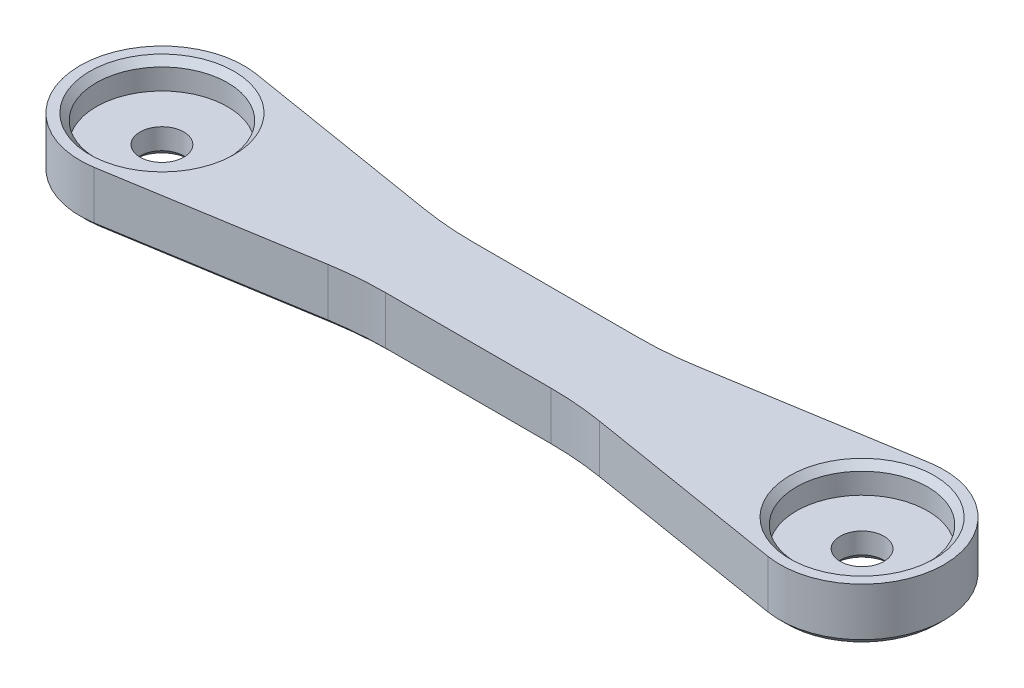
SolidWorks part; units mm, degrees
material "PLA"
ref_plane "Front Plane" through (0, 0, 0) normal (0, 0, 1) x (1, 0, 0)
ref_plane "Top Plane" through (0, 0, 0) normal (0, 1, 0) x (1, 0, 0)
ref_plane "Right Plane" through (0, 0, 0) normal (1, 0, 0) x (0, 0, -1)
sketch "Sketch1" plane through (0, 0, 0) normal (0, 1, 0) x (1, 0, 0)
  line L0 (-10, 4) -> (10, 4)
  line L1 (-32, -3) -> (32, -3) construction
  line L2 (-32, -3) -> (-32, 3) construction
  line L3 (-32, 3) -> (32, 3) construction
  line L4 (32, -3) -> (32, 3) construction
  line L5 (-32, -3) -> (32, 3) construction
  line L6 (-32, 3) -> (32, -3) construction
  line L7 (10, -4) -> (-10, -4)
  line L8 (-30.7889, 7.4016) -> (-10, 4)
  line L9 (-30.7889, -7.4016) -> (-10, -4)
  line L10 (30.7889, 7.4016) -> (10, 4)
  line L11 (30.7889, -7.4016) -> (10, -4)
  line L12 (0, 4) -> (0, -4) construction
  circle A0 centre (-32, 0) radius 7.5 construction
  circle A1 centre (32, 0) radius 7.5 construction
  circle A2 centre (-32, 0) radius 6
  circle A3 centre (32, 0) radius 6
  arc A4 (-30.7889, 7.4016) -> (-30.7889, -7.4016) centre (-32, 0) ccw
  arc A5 (30.7889, 7.4016) -> (30.7889, -7.4016) centre (32, 0) cw
  circle A6 centre (-32, 0) radius 2
  circle A7 centre (32, 0) radius 2
  point P0 (0, 0)
  point P26 (0, 0)
  dimension "D1" = 12
  dimension "D2" = 12
  dimension "D3" = 1.5
  dimension "D4" = 1.5
  dimension "D9" = 4
  dimension "D10" = 4
  dimension "D5" = 8
  dimension "D6" = 64
  dimension "D7" = 10
extrude "Boss-Extrude1" add sketch "Sketch1" against normal blind 5 contours A6 | A7 | A4 L9 L7 L11 A5 L10 L0 L8 region at (-32, 0, 0) region at (32, 0, 0)
extrude "Cut-Extrude1" cut sketch "Sketch1<3>" against normal blind 2.5 contours A3 | A2 region at (-37.8303, 0, 0) region at (26.1697, 0, 0)
sketch "Sketch1<3>" plane through (0, 0, 0) normal (0, 1, 0) x (1, 0, 0) same geometry as "Sketch1"
fillet "Fillet1" radius 30 4 edges at (10, -2.5, -4) (-10, -2.5, -4) (10, -2.5, 4) (-10, -2.5, 4)
chamfer "Chamfer1" distance 0.6 angle 45 14 edges at (-39.5, -5, 0) (-21.5975, -5, 5.8976) (0, -5, 4) (21.5975, -5, 5.8976) (39.5, -5, 0) (21.5975, -5, -5.8976) (0, -5, -4) (-21.5975, -5, -5.8976) (-32, -5, 2) (32, -5, 2) (-9.992, -5, 4.0986) (9.992, -5, 4.0986) (9.992, -5, -4.0986) (-9.992, -5, -4.0986)
chamfer "Chamfer2" distance 0.6 angle 45 2 edges at (32, 0, 6) (-32, 0, 6)
